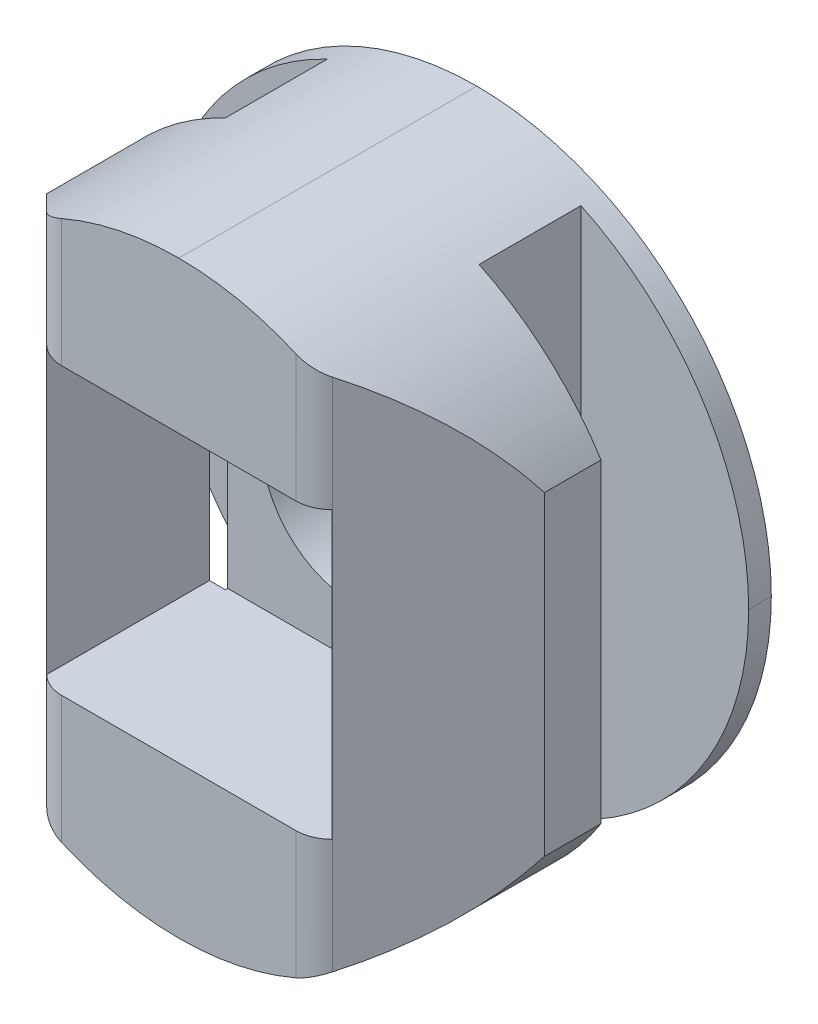
SolidWorks part; units mm, degrees
ref_plane "Front Plane" through (0, 0, 0) normal (0, 0, 1) x (1, 0, 0)
ref_plane "Top Plane" through (0, 0, 0) normal (0, 1, 0) x (1, 0, 0)
ref_plane "Right Plane" through (0, 0, 0) normal (1, 0, 0) x (0, 0, -1)
sketch "Sketch1" plane through (0, 0, 0) normal (0, 1, 0) x (1, 0, 0)
  line L0 (-11.4937, -10.6187) -> (10.6187, 11.4937) construction
  line L1 (-3.875, -3.875) -> (3.875, -3.875) construction
  line L2 (-3.875, -3.875) -> (-3.875, 3.875) construction
  line L3 (-3.875, 3.875) -> (3.875, 3.875) construction
  line L4 (3.875, -3.875) -> (3.875, 3.875) construction
  line L5 (-3.875, -3.875) -> (3.875, 3.875) construction
  line L6 (-3.875, 3.875) -> (3.875, -3.875) construction
  line L7 (-10, -10) -> (10, -10) construction
  line L8 (-10, -10) -> (-10, 10) construction
  line L9 (-10, 10) -> (10, 10) construction
  line L10 (10, -10) -> (10, 10) construction
  line L11 (-10, -10) -> (10, 10) construction
  line L12 (-10, 10) -> (10, -10) construction
  line L13 (-3, 10) -> (3, 10) construction
  line L14 (-3, 10) -> (-3, 3.875) construction
  line L16 (3, 10) -> (3, 3.875) construction
  line L17 (10.6187, -10.6187) -> (10.6187, 11.4937) construction
  line L18 (-11.4937, -10.6187) -> (10.6187, -10.6187) construction
  line L19 (3.2929, 4.1679) -> (7.225, 8.1)
  line L20 (7.225, 8.1) -> (7.225, 10) construction
  line L21 (7.225, 8.1) -> (3, 8.1)
  line L22 (3, 8.1) -> (3, 10)
  line L23 (3, 10) -> (10, 10)
  line L24 (10, 3) -> (10, 10)
  line L25 (8.1, 3) -> (10, 3)
  line L26 (8.1, 7.225) -> (8.1, 3)
  line L27 (4.1679, 3.2929) -> (8.1, 7.225)
  line L28 (3.2929, -4.1679) -> (7.225, -8.1)
  line L29 (7.225, -8.1) -> (3, -8.1)
  line L30 (3, -8.1) -> (3, -10)
  line L31 (3, -10) -> (10, -10)
  line L32 (10, -3) -> (10, -10)
  line L33 (8.1, -3) -> (10, -3)
  line L34 (8.1, -7.225) -> (8.1, -3)
  line L35 (4.1679, -3.2929) -> (8.1, -7.225)
  line L36 (-4.1679, -3.2929) -> (-8.1, -7.225)
  line L37 (-8.1, -7.225) -> (-8.1, -3)
  line L38 (-8.1, -3) -> (-10, -3)
  line L39 (-10, -3) -> (-10, -10)
  line L40 (-3, -10) -> (-10, -10)
  line L41 (-3, -8.1) -> (-3, -10)
  line L42 (-7.225, -8.1) -> (-3, -8.1)
  line L43 (-3.2929, -4.1679) -> (-7.225, -8.1)
  line L44 (-3.2929, 4.1679) -> (-7.225, 8.1)
  line L45 (-7.225, 8.1) -> (-3, 8.1)
  line L46 (-3, 8.1) -> (-3, 10)
  line L47 (-3, 10) -> (-10, 10)
  line L48 (-10, 3) -> (-10, 10)
  line L49 (-8.1, 3) -> (-10, 3)
  line L50 (-8.1, 7.225) -> (-8.1, 3)
  line L51 (-4.1679, 3.2929) -> (-8.1, 7.225)
  line L52 (-2.5858, 3.875) -> (2.5858, 3.875)
  line L53 (3.875, 2.5858) -> (3.875, -2.5858)
  line L54 (2.5858, -3.875) -> (-2.5858, -3.875)
  line L55 (-3.875, -2.5858) -> (-3.875, 2.5858)
  circle A0 centre (0, 0) radius 2.45
  arc A1 (-2.5858, 3.875) -> (-3.2929, 4.1679) centre (-2.5858, 4.875) cw
  arc A2 (3.2929, 4.1679) -> (2.5858, 3.875) centre (2.5858, 4.875) cw
  arc A3 (3.875, 2.5858) -> (4.1679, 3.2929) centre (4.875, 2.5858) cw
  arc A4 (3.875, -2.5858) -> (4.1679, -3.2929) centre (4.875, -2.5858) ccw
  arc A5 (2.5858, -3.875) -> (3.2929, -4.1679) centre (2.5858, -4.875) cw
  arc A6 (-2.5858, -3.875) -> (-3.2929, -4.1679) centre (-2.5858, -4.875) ccw
  arc A7 (-3.875, -2.5858) -> (-4.1679, -3.2929) centre (-4.875, -2.5858) cw
  arc A8 (-3.875, 2.5858) -> (-4.1679, 3.2929) centre (-4.875, 2.5858) ccw
  point P0 (0, 0)
  point P18 (0, 10)
  point P57 (0, 0)
  point P62 (3.875, 3)
  dimension "D2" = 4.9
  dimension "D7" = 1
  dimension "D8" = 1
  dimension "D1" = 7.75
  dimension "D3" = 20
  dimension "D4" = 6
  dimension "D5" = 1.9
  dimension "D6" = 4
sketch "Sketch2" plane through (0, 0, 0) normal (0, 1, 0) x (1, 0, 0)
  line L0 (-2.8, 10) -> (-2.8, 10.15)
  line L1 (-2.8, 10.15) -> (-6.5, 10.15)
  line L2 (-6.5, 10.15) -> (-6.5, 10.65)
  line L3 (-6.5, 10.65) -> (6.5, 10.65)
  line L4 (6.5, 10.65) -> (6.5, 10.15)
  line L5 (6.5, 10.15) -> (2.8, 10.15)
  line L6 (2.8, 10.15) -> (2.8, 10)
  line L7 (3, 10) -> (10, 10) construction
  line L8 (5.4922, 7.9) -> (5.4922, 6.65)
  line L9 (5.4922, 6.65) -> (-5.4922, 6.65) construction
  line L10 (-5.4922, 6.65) -> (-5.4922, 7.9)
  line L11 (-6.7422, 7.9) -> (-5.4922, 7.9) construction
  line L12 (-5.4922, 6.65) -> (-6.7422, 7.9) construction
  line L13 (5.4922, 7.9) -> (6.7422, 7.9) construction
  line L14 (2.8, 10) -> (2.8, 7.9)
  line L15 (2.8, 7.9) -> (6.7422, 7.9)
  line L16 (6.7422, 7.9) -> (3.1515, 4.3093)
  line L17 (2.5858, 4.075) -> (-2.5858, 4.075)
  line L18 (-3.1515, 4.3093) -> (-6.7422, 7.9)
  line L19 (-6.7422, 7.9) -> (-2.8, 7.9)
  line L20 (-2.8, 7.9) -> (-2.8, 10)
  line L21 (2.8, 10) -> (2.8, 7.9)
  line L22 (2.8, 7.9) -> (5.4922, 7.9)
  line L23 (5.4922, 6.65) -> (3.1515, 4.3093)
  line L24 (2.5858, 4.075) -> (-2.5858, 4.075)
  line L25 (-3.1515, 4.3093) -> (-5.4922, 6.65)
  line L26 (-5.4922, 7.9) -> (-2.8, 7.9)
  line L27 (-2.8, 7.9) -> (-2.8, 10)
  line L28 (6.7422, 7.9) -> (5.4922, 6.65) construction
  arc A4 (2.5858, 4.075) -> (3.1515, 4.3093) centre (2.5858, 4.875) ccw
  arc A5 (-3.1515, 4.3093) -> (-2.5858, 4.075) centre (-2.5858, 4.875) ccw
  arc A6 (2.5858, 4.075) -> (3.1515, 4.3093) centre (2.5858, 4.875) ccw
  arc A7 (-3.1515, 4.3093) -> (-2.5858, 4.075) centre (-2.5858, 4.875) ccw
  dimension "D2" = 13
  dimension "D3" = 0.5
  dimension "D4" = 0.15
  dimension "D5" = 1.25
  dimension "D1" = 0.2
extrude "Boss-Extrude1" add sketch "Sketch2" along normal mid plane 13
sketch "Sketch5" plane through (0, 0, -10.65) normal (0, 0, -1) x (-1, 0, 0)
  circle A0 centre (0, 0) radius 2.05
  dimension "D1" = 4.1
extrude "Cut-Extrude2" cut sketch "Sketch5" against normal through all
sketch "Sketch6" plane through (0, 0, -10.65) normal (0, 0, -1) x (-1, 0, 0)
  circle A0 centre (0, 0) radius 3.05
  dimension "D1" = 6.1
extrude "Cut-Extrude3" cut sketch "Sketch6" against normal blind 0.2
fillet "Fillet1" radius 6.5 4 edges at (6.5, -6.5, -10.4) (-6.5, -6.5, -10.4) (6.5, 6.5, -10.4) (-6.5, 6.5, -10.4)
sketch "Sketch7" plane through (0, 0, -4.075) normal (0, 0, 1) x (1, 0, 0)
  line L1 (-3.15, -3.15) -> (3.15, -3.15)
  line L2 (-3.15, -3.15) -> (-3.15, 3.15)
  line L3 (-3.15, 3.15) -> (3.15, 3.15)
  line L4 (3.15, -3.15) -> (3.15, 3.15)
  line L5 (-3.15, -3.15) -> (3.15, 3.15) construction
  line L6 (-3.15, 3.15) -> (3.15, -3.15) construction
  point P0 (0, 0)
  dimension "D1" = 6.3
extrude "Cut-Extrude4" cut sketch "Sketch7" against normal offset from surface (3.875 mm away) 2.5 up to face at (-3.05, 0, -10.45)
